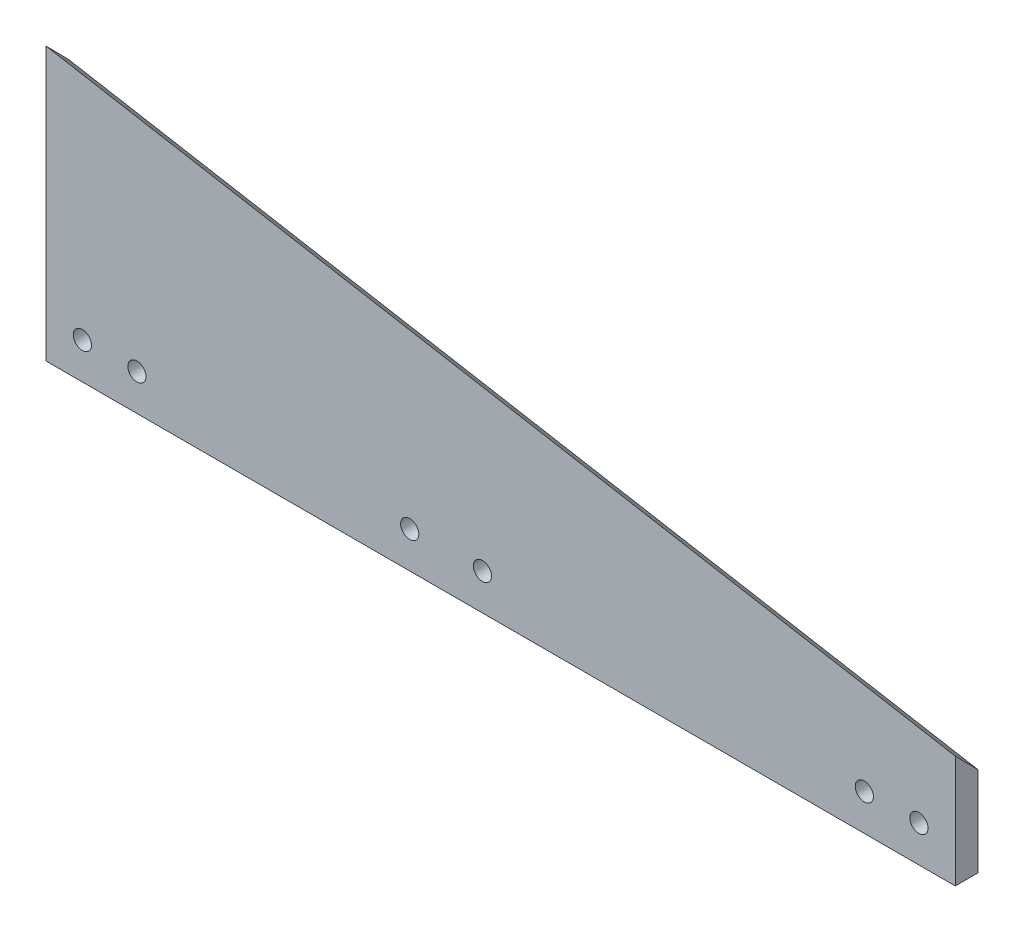
SolidWorks part; units mm, degrees
ref_plane "Front Plane" through (0, 0, 0) normal (0, 0, 1) x (1, 0, 0)
ref_plane "Top Plane" through (0, 0, 0) normal (0, 1, 0) x (1, 0, 0)
ref_plane "Right Plane" through (0, 0, 0) normal (1, 0, 0) x (0, 0, -1)
sketch "Sketch1" plane through (0, 0, 0) normal (1, 0, 0) x (0, 0, -1)
  line L1 (-5, 60) -> (0, 60)
  line L2 (-5, 60) -> (-5, 0)
  line L3 (-5, 0) -> (0, 0)
  line L4 (0, 60) -> (0, 0)
  dimension "D1" = 5
  dimension "D2" = 60
extrude "Boss-Extrude1" add sketch "Sketch1" along normal blind 200
sketch "Sketch3" plane through (0, 0, 5) normal (0, 0, 1) x (1, 0, 0)
  line L0 (0, 60) -> (200, 60)
  line L1 (200, 60) -> (200, 24.7346)
  line L2 (200, 60) -> (200, 0) construction
  line L3 (200, 24.7346) -> (0, 60)
  line L4 (200, 45.8938) -> (80, 45.8938) construction
  dimension "D1" = 10
  dimension "D2" = 120
extrude "Cut-Extrude2" cut sketch "Sketch3" against normal up to surface (5 mm away) up to face at (100, 30, 0)
chamfer "Chamfer1" distance 5 angle 45 1 edges at (100, 42.3673, 0)
sketch "Sketch2" plane through (0, 0, 0) normal (0, 0, -1) x (-1, 0, 0)
  line L1 (-200, 0) -> (0, 0) construction
  line L2 (-200, 0) -> (-200, 19.6575) construction
  circle A0 centre (-192, 8) radius 2
  circle A1 centre (-180, 8) radius 2
  dimension "D1" = 4
  dimension "D2" = 8
  dimension "D3" = 8
  dimension "D4" = 12
extrude "Cut-Extrude1" cut sketch "Sketch2" against normal up to surface (5 mm away) up to face at (100, 21.1837, 5)
ref_plane "Plane1" through (100, 0, 0) normal (1, 0, 0) x (0, 0, -1)
mirror "Mirror2" about plane through (100, 0, 0) normal (1, 0, 0) of "Cut-Extrude1"
sketch "Sketch4" plane through (0, 0, 0) normal (0, 0, -1) x (-1, 0, 0)
  line L0 (-200, 0) -> (-200, 19.6575) construction
  circle A2 centre (-80, 8) radius 2
  circle A3 centre (-96, 8) radius 2
  dimension "D1" = 4
  dimension "D3" = 16
  dimension "D2" = 120
extrude "Cut-Extrude3" cut sketch "Sketch4" against normal up to surface (5 mm away) up to face at (8, 10, 5)
